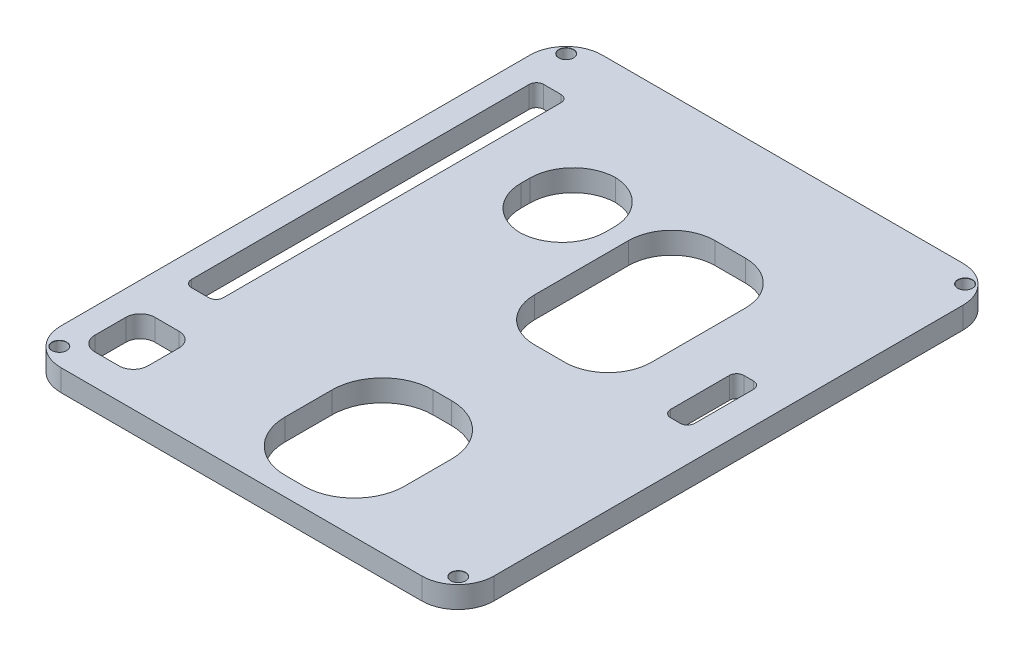
SolidWorks part; units mm, degrees
ref_plane "Ebene vorne" through (0, 0, 0) normal (0, 0, 1) x (1, 0, 0)
ref_plane "Ebene oben" through (0, 0, 0) normal (0, 1, 0) x (1, 0, 0)
ref_plane "Ebene rechts" through (0, 0, 0) normal (1, 0, 0) x (0, 0, -1)
sketch "Skizze1" plane through (0, 0, 0) normal (0, 1, 0) x (1, 0, 0)
  line L1 (-30, -37.5) -> (30, -37.5)
  line L2 (-30, -37.5) -> (-30, 37.5)
  line L3 (-30, 37.5) -> (30, 37.5)
  line L4 (30, -37.5) -> (30, 37.5)
  line L5 (-30, -37.5) -> (30, 37.5) construction
  line L6 (-30, 37.5) -> (30, -37.5) construction
  point P0 (0, 0)
  dimension "D1" = 60
  dimension "D2" = 75
extrude "Aufsatz-Linear austragen1" add sketch "Skizze1" along normal blind 3
fillet "Verrundung1" radius 5 4 edges at (30, 1.5, 37.5) (-30, 1.5, 37.5) (-30, 1.5, -37.5) (30, 1.5, -37.5)
hole_wizard "Ø2.0 (2) Durchmesser Bohrung1" positions "Skizze2" profile "Skizze3" hole size "Ø2.0" standard "DIN"
sketch "Skizze2" plane through (0, 3, 0) normal (0, 1, 0) x (0, 0, 1)
  point P0 (-35.1659, 27.6025)
  point P2 (35.0543, 27.6025)
  point P4 (35.0543, -27.6583)
  point P6 (-35.1659, -27.6583)
sketch "Skizze3" plane through (27.6025, 3, -35.1659) normal (1, 0, 0) x (0, 0, 1)
  line L0 (0, 0) -> (0, 20.6009)
  line L1 (0, 20.6009) -> (1, 20)
  line L2 (1, 20) -> (1, 0.025)
  line L3 (1, 0.025) -> (1.025, 0)
  line L4 (1.025, 0) -> (0, 0)
  line L5 (-1, 0.025) -> (-1.025, 0) construction
  line L6 (0, 20.6009) -> (-1, 20) construction
  line L7 (0, -6.35) -> (0, 107.95) construction
  dimension "Bohrerdurchmesser" = 2
  dimension "Bohrungstiefe" = 20
  dimension "Senkdurchmesser2 (Oben)" = 2.05
  dimension "Senkwinkel2 (Oben)" = 90
  dimension "Spitzenwinkel" = 118
extrude "Schnitt-Linear austragen1" cut sketch "Skizze4" against normal blind 5
sketch "Skizze4" plane through (0, 3, 0) normal (0, 1, 0) x (0, 0, 1)
  line L1 (-23.0532, 15.2746) -> (1.9537, 15.2746)
  line L2 (-23.0532, 15.2746) -> (-23.0532, -0.921)
  line L3 (-23.0532, -0.921) -> (1.9537, -0.921)
  line L4 (1.9537, 15.2746) -> (1.9537, -0.921)
  line L5 (24.9511, -19.1738) -> (33.2681, -19.1738)
  line L6 (24.9511, -19.1738) -> (24.9511, -26.5355)
  line L7 (24.9511, -26.5355) -> (33.2681, -26.5355)
  line L8 (33.2681, -19.1738) -> (33.2681, -26.5355)
  line L9 (14.4013, 13.0337) -> (34.8868, 13.0337)
  line L10 (14.4013, 13.0337) -> (14.4013, -3.5445)
  line L11 (14.4013, -3.5445) -> (34.8868, -3.5445)
  line L12 (34.8868, 13.0337) -> (34.8868, -3.5445)
  line L13 (-8.8752, 25.593) -> (1.2838, 25.593)
  line L14 (-8.8752, 25.593) -> (-8.8752, 22.2438)
  line L15 (-8.8752, 22.2438) -> (1.2838, 22.2438)
  line L16 (1.2838, 25.593) -> (1.2838, 22.2438)
  line L17 (-29.9189, -22.1322) -> (18.8668, -22.1322)
  line L18 (-29.9189, -22.1322) -> (-29.9189, -26.5355)
  line L19 (-29.9189, -26.5355) -> (18.8668, -26.5355)
  line L20 (18.8668, -22.1322) -> (18.8668, -26.5355)
  line L21 (-23.723, -3.5445) -> (-10.4897, -3.5445)
  line L22 (-23.723, -3.5445) -> (-23.723, -15.2543)
  line L23 (-23.723, -15.2543) -> (-10.4897, -15.2543)
  line L24 (-10.4897, -3.5445) -> (-10.4897, -15.2543)
fillet "Verrundung2" radius 6 12 edges at (-15.2543, 1.5, -23.723) (-3.5445, 1.5, -23.723) (-3.5445, 1.5, -10.4897) (-15.2543, 1.5, -10.4897) (-9.3994, 3, -23.723) (-9.3994, 3, -10.4897) (-0.921, 1.5, -23.0532) (15.2746, 1.5, -23.0532) (15.2746, 1.5, 1.9537) (-0.921, 1.5, 1.9537) (-9.3994, 0, -10.4897) (-9.3994, 0, -23.723)
fillet "Verrundung3" radius 1 8 edges at (-26.5355, 1.5, -29.9189) (-22.1322, 1.5, -29.9189) (-22.1322, 1.5, 18.8668) (-26.5355, 1.5, 18.8668) (22.2438, 1.5, -8.8752) (25.593, 1.5, -8.8752) (25.593, 1.5, 1.2838) (22.2438, 1.5, 1.2838)
fillet "Verrundung4" radius 7 4 edges at (-3.5445, 1.5, 14.4013) (13.0337, 1.5, 14.4013) (13.0337, 1.5, 34.8868) (-3.5445, 1.5, 34.8868)
fillet "Verrundung5" radius 2 4 edges at (-26.5355, 1.5, 24.9511) (-19.1738, 1.5, 24.9511) (-19.1738, 1.5, 33.2681) (-26.5355, 1.5, 33.2681)
